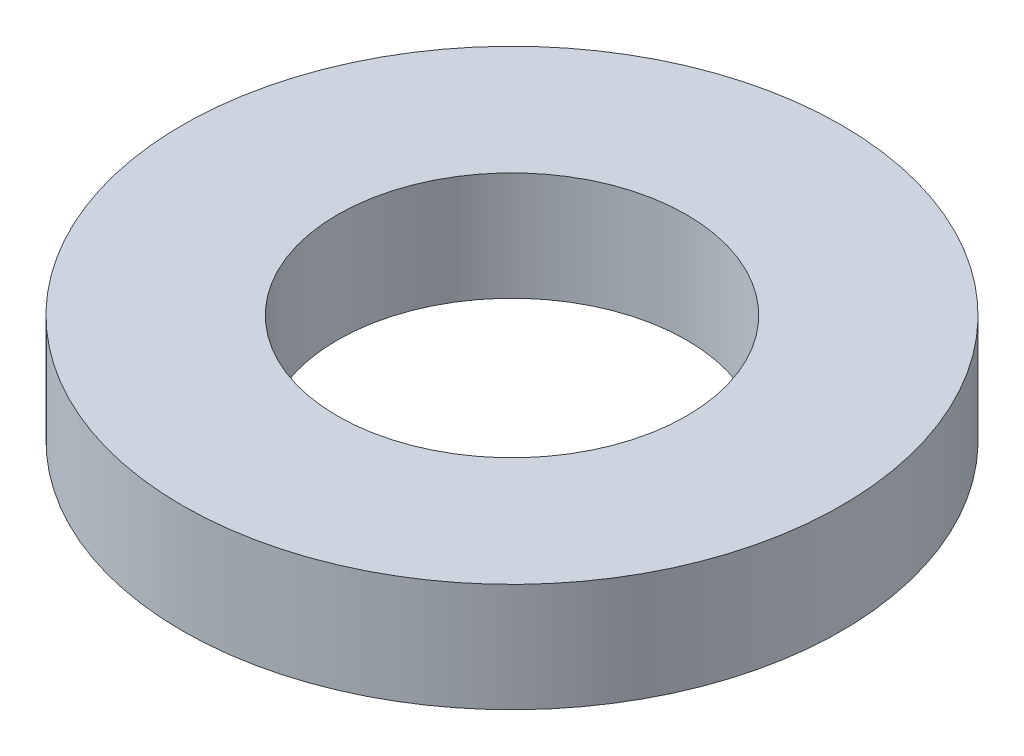
SolidWorks part; units mm, degrees
ref_plane "Front Plane" through (0, 0, 0) normal (0, 0, 1) x (1, 0, 0)
ref_plane "Top Plane" through (0, 0, 0) normal (0, 1, 0) x (1, 0, 0)
ref_plane "Right Plane" through (0, 0, 0) normal (1, 0, 0) x (0, 0, -1)
sketch "Sketch1" plane through (0, 0, 0) normal (0, 1, 0) x (1, 0, 0)
  circle A0 centre (0, 0) radius 42.5
  dimension "FLANGE_OD" = 85
extrude "Boss-Extrude1" add sketch "Sketch1" along normal blind 14
sketch "Sketch2" plane through (0, 0, 0) normal (0, 1, 0) x (1, 0, 0)
  circle A0 centre (0, 0) radius 22.5
  dimension "BORE_D" = 45
extrude "Cut-Extrude1" cut sketch "Sketch2" along normal through all
sketch "Sketch3" plane through (0, 14, 0) normal (0, 1, 0) x (1, 0, 0)
  circle A0 centre (0, 0) radius 16.676 construction
  circle A1 centre (-16.676, 0) radius 2.4344
  dimension "BOLT_D" = 4.8687
  dimension "BOLT_PCD" = 33.352
extrude "Cut-Extrude2" cut sketch "Sketch3" against normal blind 8.4125 rebuild error yes
pattern_circular "CirPattern1" count 3 over 360 rebuild error yes
